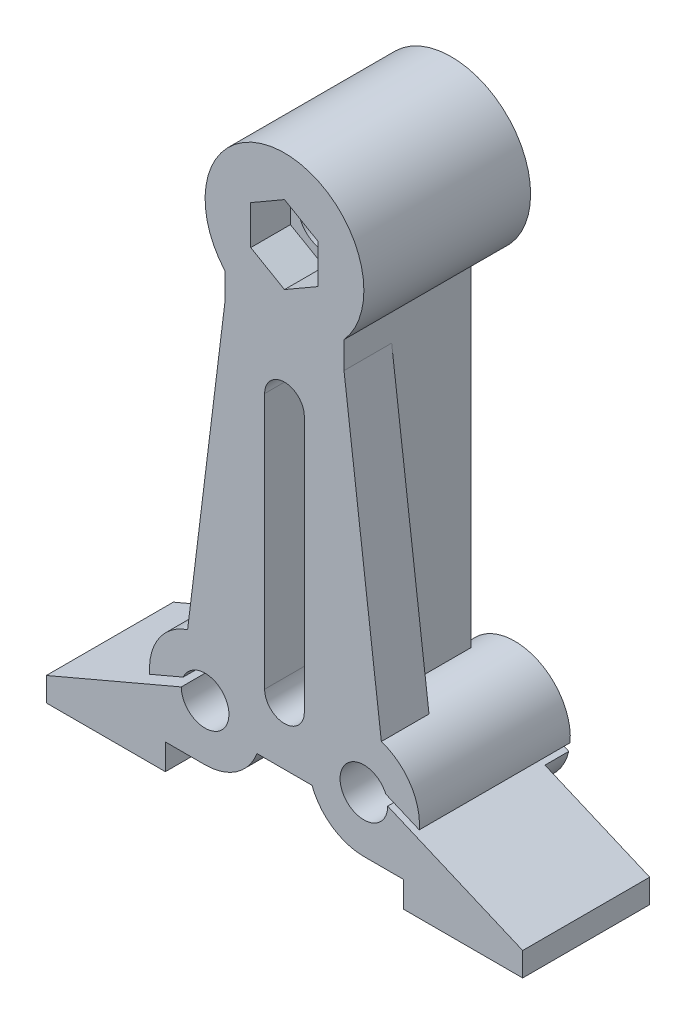
SolidWorks part; units mm, degrees
ref_plane "Front Plane" through (0, 0, 0) normal (0, 0, 1) x (1, 0, 0)
ref_plane "Top Plane" through (0, 0, 0) normal (0, 1, 0) x (1, 0, 0)
ref_plane "Right Plane" through (0, 0, 0) normal (1, 0, 0) x (0, 0, -1)
sketch "Sketch1" plane through (0, 0, 0) normal (0, 0, 1) x (1, 0, 0)
  line L0 (0, -47.8538) -> (0, 47.8538) construction
  line L1 (10, -14.5) -> (15, -14.5)
  line L2 (15, -14.5) -> (15, -17.75)
  line L3 (15, -17.75) -> (30, -17.75)
  line L4 (30, -17.75) -> (30, -14.75)
  line L5 (30, -14.75) -> (13, -7.5) construction
  line L6 (0, -5) -> (3.4617, -5)
  line L7 (3.4617, -5) -> (3.4617, -10) construction
  line L8 (3.4617, -10) -> (0, -10)
  line L9 (30, -14.75) -> (16.8089, -9.1244)
  line L10 (0, -10) -> (0, -5)
  circle A0 centre (10, -7.5) radius 7
  point P5 (0, 0)
  point P15 (3.4617, -7.5)
  dimension "D1" = 14
  dimension "D2" = 20
  dimension "D3" = 15
  dimension "D4" = 3
  dimension "D5" = 3.25
  dimension "D6" = 7.5
  dimension "D7" = 30
  dimension "D8" = 3
  dimension "D9" = 5
extrude "Boss-Extrude1" add sketch "Sketch1" along normal blind 16 contours A0 L1 L2 L3 L4 L9 | A0 | A0 L6 L10 L8 region at (21.2062, -14.5589, 0) region at (10, -7.5, 0) region at (1.5789, -7.5, 0)
sketch "Sketch3" plane through (0, 0, 0) normal (0, 0, 1) x (1, 0, 0)
  circle A0 centre (10, -7.5) radius 7
  arc A1 (16.8089, -9.1244) -> (3.4617, -5) centre (10, -7.5) ccw construction
extrude "Boss-Extrude2" add sketch "Sketch3" against normal blind 3
sketch "Sketch2" plane through (0, 0, 0) normal (0, 0, 1) x (1, 0, 0)
  line L0 (13, -7.5) -> (16.9597, -9.1887)
  line L1 (16.9597, -9.1887) -> (17.352, -8.2689)
  line L2 (17.352, -8.2689) -> (12.7528, -6.3074)
  line L3 (30, -14.75) -> (16.8089, -9.1244) construction
  line L4 (30, -14.75) -> (16.8089, -9.1244) construction
  arc A0 (16.8089, -9.1244) -> (3.4617, -5) centre (10, -7.5) ccw construction
  arc A1 (16.8089, -9.1244) -> (3.4617, -5) centre (10, -7.5) ccw construction
  circle A2 centre (10, -7.5) radius 3
  dimension "D1" = 6
  dimension "D2" = 1
  dimension "D3" = 5
extrude "Cut-Extrude1" cut sketch "Sketch2" along normal through all both and the other way through all contours A2 | A2 L0 L1 L2 region at (15.0404, -7.8131, 0) region at (10, -7.5, 0)
sketch "Sketch4" plane through (0, 0, 16) normal (0, 0, 1) x (1, 0, 0)
  line L0 (12.9774, -7.1325) -> (7.5, 37.25) construction
  line L1 (0, -10) -> (0, 75.1129) construction
  line L2 (0, -2.5) -> (0, 29.75) construction
  line L3 (7.5, 40.6356) -> (7.5, -0.9617)
  line L4 (2.5, -2.5) -> (2.5, 29.75)
  line L5 (12.2028, -0.8556) -> (7.5, 37.25)
  line L6 (0, -5) -> (3.4617, -5) construction
  line L7 (3.4617, -5) -> (0, -5)
  line L8 (0, 32.25) -> (0, 44.85)
  line L9 (0, 49.65) -> (0, 57.25)
  circle A0 centre (10, -7.5) radius 3 construction
  arc A1 (3.4617, -5) -> (12.2028, -0.8556) centre (10, -7.5) cw
  arc A2 (12.7528, -6.3074) -> (13, -7.5) centre (10, -7.5) ccw construction
  arc A3 (0, 57.25) -> (0, 37.25) centre (0, 47.25) cw
  arc A4 (0, 49.65) -> (0, 44.85) centre (0, 47.25) cw
  arc A5 (0, -5) -> (2.5, -2.5) centre (0, -2.5) ccw
  arc A6 (2.5, 29.75) -> (0, 32.25) centre (0, 29.75) ccw
  arc A7 (16.9736, -8.1075) -> (3.4617, -5) centre (10, -7.5) ccw construction
  arc A8 (16.9736, -8.1075) -> (3.4617, -5) centre (10, -7.5) ccw construction
  arc M9 (16.9736, -8.1075) -> (3.4617, -5) centre (10, -7.5) ccw
  line M10 (3.4617, -5) -> (0, -5)
  dimension "D1" = 10
  dimension "D2" = 2.4
  dimension "D3" = 54.75
  dimension "D4" = 32.25
  dimension "D5" = 5
  dimension "D6" = 5
  dimension "D7" = 5
extrude "Boss-Extrude3" add sketch "Sketch4" against normal blind 6 contours L5 L3 M9 region at (9.0563, 11.9929, 16)
extrude "Boss-Extrude4" add sketch "Sketch4<6>" against normal blind 16 contours A6 L4 A5 L3 A3 L8 M10 M9 region at (4.7327, 18.8243, 16)
sketch "Sketch4<6>" plane through (0, 0, 16) normal (0, 0, 1) x (1, 0, 0) same geometry as "Sketch4"
extrude "Boss-Extrude5" add sketch "Sketch4<7>" against normal blind 21 contours L9 A4 L8 A3 region at (4.4413, 47.25, 16)
sketch "Sketch4<7>" plane through (0, 0, 16) normal (0, 0, 1) x (1, 0, 0) same geometry as "Sketch4"
mirror "Mirror1" about plane through (0, 0, 0) normal (1, 0, 0) of bodies 114
sketch "Sketch5" plane through (0, 0, 16) normal (0, 0, 1) x (1, 0, 0)
  line L1 (4.25, 49.7037) -> (0, 52.1575)
  line L2 (0, 52.1575) -> (-4.25, 49.7037)
  line L3 (-4.25, 49.7037) -> (-4.25, 44.7963)
  line L4 (-4.25, 44.7963) -> (0, 42.3425)
  line L5 (0, 42.3425) -> (4.25, 44.7963)
  line L6 (4.25, 44.7963) -> (4.25, 49.7037)
  circle A0 centre (0, 47.25) radius 2.4 construction
  circle A1 centre (0, 47.25) radius 2.4 construction
  circle A2 centre (0, 47.25) radius 4.25 construction
  dimension "D1" = 8.5
extrude "Cut-Extrude2" cut sketch "Sketch5" against normal blind 5
extrude "Cut-Extrude3" cut sketch "Sketch5<2>" along normal blind 5 from surface starting at face at (2.4, 47.25, -5)
sketch "Sketch5<2>" plane through (0, 0, 16) normal (0, 0, 1) x (1, 0, 0) same geometry as "Sketch5"
sketch "Sketch6" plane through (0, 0, 11) normal (0, 0, 1) x (1, 0, 0)
  circle A0 centre (0, 47.25) radius 2.4 construction
  circle A1 centre (0, 47.25) radius 2.4 construction
  circle A2 centre (0, 47.25) radius 3.25
  dimension "D1" = 6.5
extrude "Cut-Extrude4" cut sketch "Sketch6" against normal through all both and the other way through all
